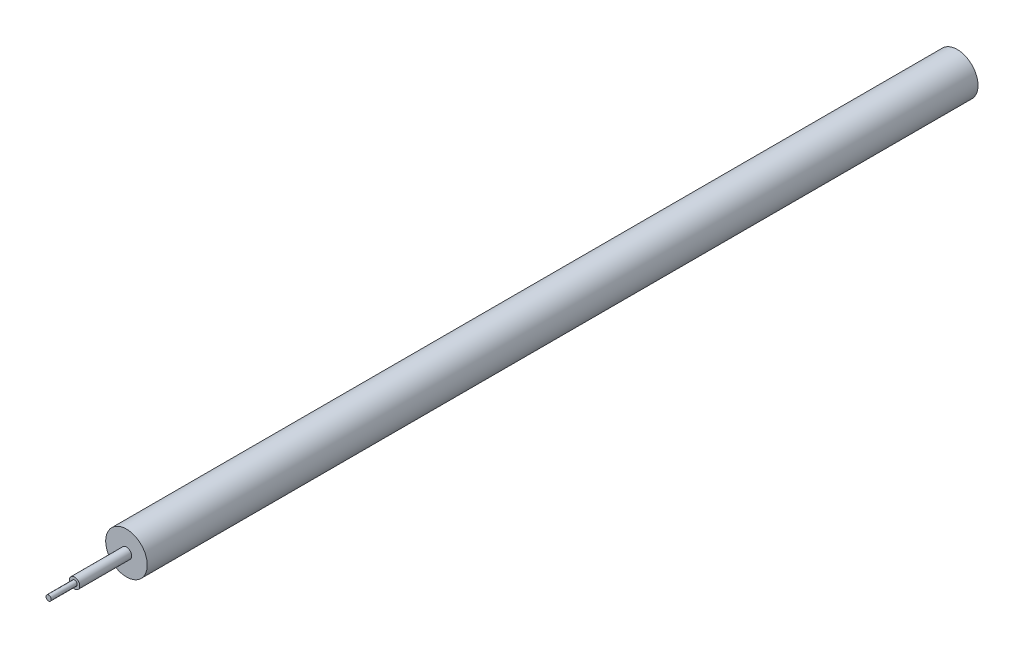
SolidWorks part; units mm, degrees
ref_plane "Front Plane" through (0, 0, 0) normal (0, 0, 1) x (1, 0, 0)
ref_plane "Top Plane" through (0, 0, 0) normal (0, 1, 0) x (1, 0, 0)
ref_plane "Right Plane" through (0, 0, 0) normal (1, 0, 0) x (0, 0, -1)
sketch "Sketch1" plane through (0, 0, 0) normal (0, 0, 1) x (1, 0, 0)
  circle A0 centre (0, 0) radius 4
  dimension "D1" = 8
extrude "Boss-Extrude1" add sketch "Sketch1" along normal blind 160
sketch "Sketch2" plane through (0, 0, 160) normal (0, 0, 1) x (1, 0, 0)
  circle A0 centre (0, 0) radius 1
  circle A1 centre (0, 0) radius 0.5
  dimension "D1" = 2
  dimension "D2" = 1
extrude "Boss-Extrude2" add sketch "Sketch2" along normal blind 10 contours A1 | A0 A1 | A0 region at (-0.9717, 0, 160) region at (0, 0, 160)
extrude "Boss-Extrude3" add sketch "Sketch2<3>" along normal blind 15 contours A1
sketch "Sketch2<3>" plane through (0, 0, 160) normal (0, 0, 1) x (1, 0, 0) same geometry as "Sketch2"
